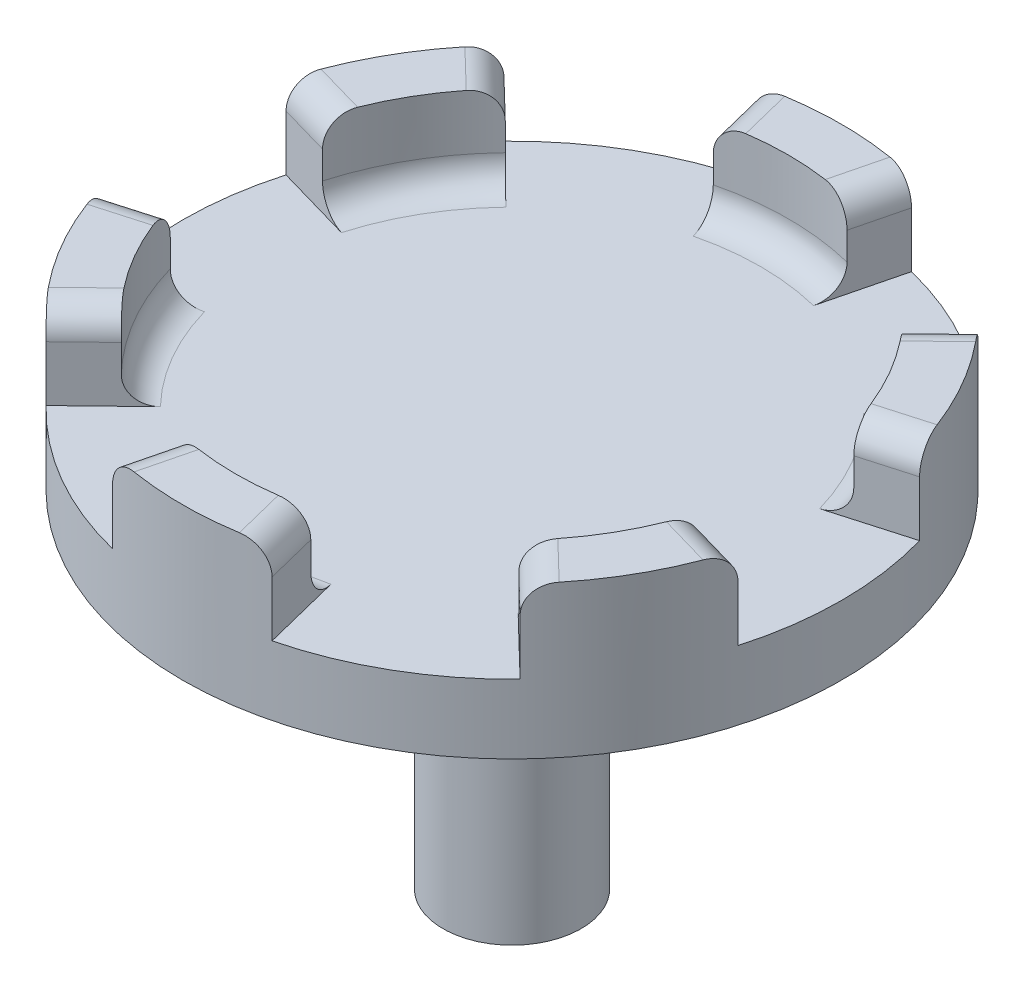
SolidWorks part; units mm, degrees
ref_plane "Front Plane" through (0, 0, 0) normal (0, 0, 1) x (1, 0, 0)
ref_plane "Top Plane" through (0, 0, 0) normal (0, 1, 0) x (1, 0, 0)
ref_plane "Right Plane" through (0, 0, 0) normal (1, 0, 0) x (0, 0, -1)
sketch "Sketch1" plane through (0, 0, 0) normal (0, 1, 0) x (1, 0, 0)
  circle A0 centre (0, 0) radius 30.2895
  dimension "D1" = 60.579
extrude "Boss-Extrude1" add sketch "Sketch1" along normal blind 6.35
sketch "Sketch2" plane through (0, 6.35, 0) normal (0, 1, 0) x (1, 0, 0)
  line L0 (-6.1482, -24.6447) -> (-7.3317, -29.3888)
  line L1 (-20.3643, -26.1375) -> (5.7009, -32.64) construction
  line L2 (-16.2324, -22.129) -> (3.936, -27.1604) construction
  line L3 (6.1482, -24.6447) -> (7.3317, -29.3888)
  line L4 (4.3414, -25.0954) -> (7.9549, -24.194) construction
  line L5 (8.1027, -29.1964) -> (6.5606, -29.5811) construction
  line L6 (-6.1482, -24.6447) -> (6.1482, -24.6447) construction
  line L7 (0, 0) -> (0, -49.2894) construction
  line L8 (-37.5524, 0) -> (37.5524, 0) construction
  line L9 (-24.417, -6.9979) -> (-29.1173, -8.345)
  line L10 (-18.2688, -17.6468) -> (-21.7856, -21.0438)
  line L11 (-18.2688, 17.6468) -> (-21.7856, 21.0438)
  line L12 (-24.417, 6.9979) -> (-29.1173, 8.345)
  line L13 (6.1482, 24.6447) -> (7.3317, 29.3888)
  line L14 (-6.1482, 24.6447) -> (-7.3317, 29.3888)
  line L15 (24.417, 6.9979) -> (29.1173, 8.345)
  line L16 (18.2688, 17.6468) -> (21.7856, 21.0438)
  line L17 (18.2688, -17.6468) -> (21.7856, -21.0438)
  line L18 (24.417, -6.9979) -> (29.1173, -8.345)
  line L19 (0, 0) -> (-6.1482, -24.6447) construction
  line L20 (0, 0) -> (-24.417, -6.9979) construction
  circle A0 centre (0, 0) radius 25.4 construction
  arc A1 (-18.2688, -17.6468) -> (-24.417, -6.9979) centre (0, 0) cw
  arc A2 (-21.7856, -21.0438) -> (-29.1173, -8.345) centre (0, 0) cw
  circle A3 centre (0, 0) radius 30.2895 construction
  arc A4 (6.1482, -24.6447) -> (-6.1482, -24.6447) centre (0, 0) cw
  arc A5 (7.3317, -29.3888) -> (-7.3317, -29.3888) centre (0, 0) cw
  arc A6 (-24.417, 6.9979) -> (-18.2688, 17.6468) centre (0, 0) cw
  arc A7 (-29.1173, 8.345) -> (-21.7856, 21.0438) centre (0, 0) cw
  arc A8 (-6.1482, 24.6447) -> (6.1482, 24.6447) centre (0, 0) cw
  arc A9 (-7.3317, 29.3888) -> (7.3317, 29.3888) centre (0, 0) cw
  arc A10 (18.2688, 17.6468) -> (24.417, 6.9979) centre (0, 0) cw
  arc A11 (21.7856, 21.0438) -> (29.1173, 8.345) centre (0, 0) cw
  arc A12 (24.417, -6.9979) -> (18.2688, -17.6468) centre (0, 0) cw
  arc A13 (29.1173, -8.345) -> (21.7856, -21.0438) centre (0, 0) cw
  point P10 (-7.3317, -29.3888)
  point P13 (-6.1482, -24.6447)
  point P18 (6.1482, -24.6447)
  point P20 (7.3317, -29.3888)
  point P23 (0, -24.6447)
  point P28 (0, 0)
  circle M16 centre (0, 0) radius 30.2895
  dimension "D1" = 50.8
  dimension "D2" = 6
  dimension "D3" = 60
extrude "Boss-Extrude2" add sketch "Sketch2" along normal blind 7.62 contours L3 A4 L0 M16 | L18 A12 L17 M16 | L16 A10 L15 M16 | L12 A6 L11 M16 | L10 A1 L9 M16 | A9 L13 A8 L14 region at (0, 6.35, 27.639) region at (-23.9361, 6.35, 13.8195) region at (23.9361, 6.35, 13.8195) region at (-23.9361, 6.35, -13.8195) region at (23.9361, 6.35, -13.8195)
fillet "Fillet1" radius 2.54 12 edges at (26.7671, 13.97, 7.6714) (26.7671, 13.97, -7.6714) (20.0272, 13.97, -19.3453) (6.7399, 13.97, -27.0167) (-6.7399, 13.97, -27.0167) (-20.0272, 13.97, -19.3453) (-26.7671, 13.97, -7.6714) (-26.7671, 13.97, 7.6714) (-20.0272, 13.97, 19.3453) (-6.7399, 13.97, 27.0167) (20.0272, 13.97, 19.3453) (6.7399, 13.97, 27.0167)
sketch "Sketch3" plane through (0, 0, 0) normal (0, -1, 0) x (1, 0, 0)
  circle A0 centre (0, 0) radius 8.89
  dimension "D1" = 17.78
extrude "Boss-Extrude3" add sketch "Sketch3" along normal blind 6.35
fillet "Fillet2" radius 2.54 6 edges at (-21.997, 6.35, 12.7) (-21.997, 6.35, -12.7) (0, 6.35, -25.4) (21.997, 6.35, -12.7) (0, 6.35, 25.4) (21.997, 6.35, 12.7)
sketch "Sketch4" plane through (0, -6.35, 0) normal (0, -1, 0) x (1, 0, 0)
  circle A0 centre (0, 0) radius 6.35
  dimension "D1" = 12.7
extrude "Boss-Extrude4" add sketch "Sketch4" along normal blind 25.4
